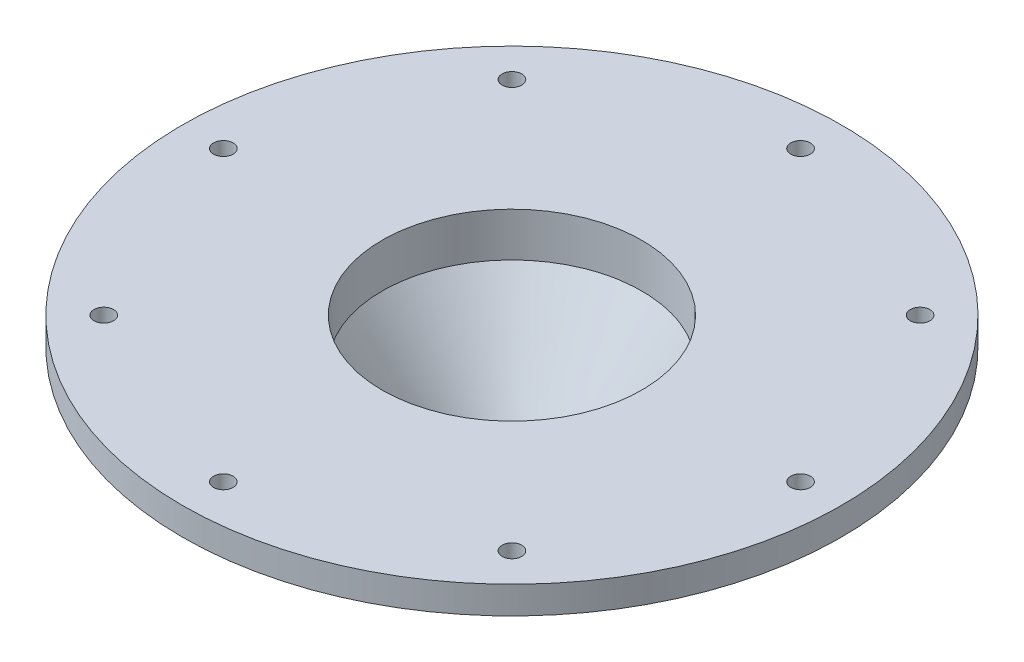
SolidWorks part; units mm, degrees
material "7075-T6 (SN)"
ref_plane "Front Plane" through (0, 0, 0) normal (0, 0, 1) x (1, 0, 0)
ref_plane "Top Plane" through (0, 0, 0) normal (0, 1, 0) x (1, 0, 0)
ref_plane "Right Plane" through (0, 0, 0) normal (1, 0, 0) x (0, 0, -1)
sketch "Sketch1" plane through (0, 0, 0) normal (0, 1, 0) x (1, 0, 0)
  circle A0 centre (0, 0) radius 38.0682
  dimension "D1" = 76.1365
extrude "Boss-Extrude1" add sketch "Sketch1" along normal blind 3.175
hole_wizard "Tap Drill for #4-40 Tap1" positions "Sketch3" profile "Sketch4" hole size "#4-40" standard "ANSI Inch" end condition through all
sketch "Sketch3" plane through (0, 0, 0) normal (0, -1, 0) x (-1, 0, 0)
  point P0 (0, -33.3375)
  dimension "D1" = 33.3375
sketch "Sketch4" plane through (0, 0, 33.3375) normal (1, 0, 0) x (0, 0, -1)
  line L0 (0, 0) -> (0, 3.175)
  line L1 (0, 3.175) -> (1.1303, 3.175)
  line L2 (1.1303, 3.175) -> (1.1303, 0)
  line L5 (1.1303, 0) -> (0, 0)
  line L11 (0, -6.35) -> (0, 107.95) construction
  dimension "Thru Hole Dia." = 2.2606
  dimension "Thru Hole Depth" = 3.175
pattern_circular "CirPattern1" count 8 over 360 about axis through (0, 0, 0) along (0, 1, 0) of "Tap Drill for #4-40 Tap1"
sketch "Sketch5" plane through (0, 0, 0) normal (0, -1, 0) x (1, 0, 0)
  circle A0 centre (0, 0) radius 25.4
  dimension "D1" = 50.8
extrude "Boss-Extrude2" add sketch "Sketch5" along normal blind 19.05
sketch "Sketch6" plane through (0, -19.05, 0) normal (0, -1, 0) x (1, 0, 0)
  circle A0 centre (0, 0) radius 5
  dimension "D1" = 10
extrude "Cut-Extrude1" cut sketch "Sketch6" against normal through all both and the other way through all
sketch "Sketch7" plane through (0, 3.175, 0) normal (0, 1, 0) x (1, 0, 0)
  circle A0 centre (0, 0) radius 15
  dimension "D1" = 30
extrude "Cut-Extrude2" cut sketch "Sketch7" against normal blind 5.08
sketch "Sketch8" plane through (0, -1.905, 0) normal (0, 1, 0) x (1, 0, 0)
  circle A0 centre (0, 0) radius 15
  circle A1 centre (0, 0) radius 15 construction
  dimension "D1" = 0
ref_plane "Plane1" through (0, -15.875, 0) normal (0, -1, 0) x (-1, 0, 0)
sketch "Sketch9" plane through (0, -15.875, 0) normal (0, -1, 0) x (-1, 0, 0)
  circle A0 centre (0, 0) radius 5
  circle A1 centre (0, 0) radius 5 construction
  dimension "D1" = 0
loft "Cut-Loft1" cut profiles "Sketch8", "Sketch9" connector at (0, -1.905, 15) connector at (-1.3659, -15.875, 4.8098)
sketch "Sketch10" plane through (0, 0, 0) normal (0, 0, 1) x (1, 0, 0)
  line L6 (0, 0) -> (0, -33.2378) construction
  line L7 (-25.4, 0) -> (-24.4, 0)
  line L8 (-25.4, 0) -> (25.4, 0) construction
  line L9 (-24.4, 0) -> (-8.4152, -19.05)
  line L10 (-25.4, -19.05) -> (25.4, -19.05) construction
  line L11 (-8.4152, -19.05) -> (-25.4, -19.05)
  line L12 (-25.4, -19.05) -> (-25.4, 0)
  dimension "D1" = 50
  dimension "D2" = 1
revolve "Cut-Revolve1" cut sketch "Sketch10" angle 360 about L6
